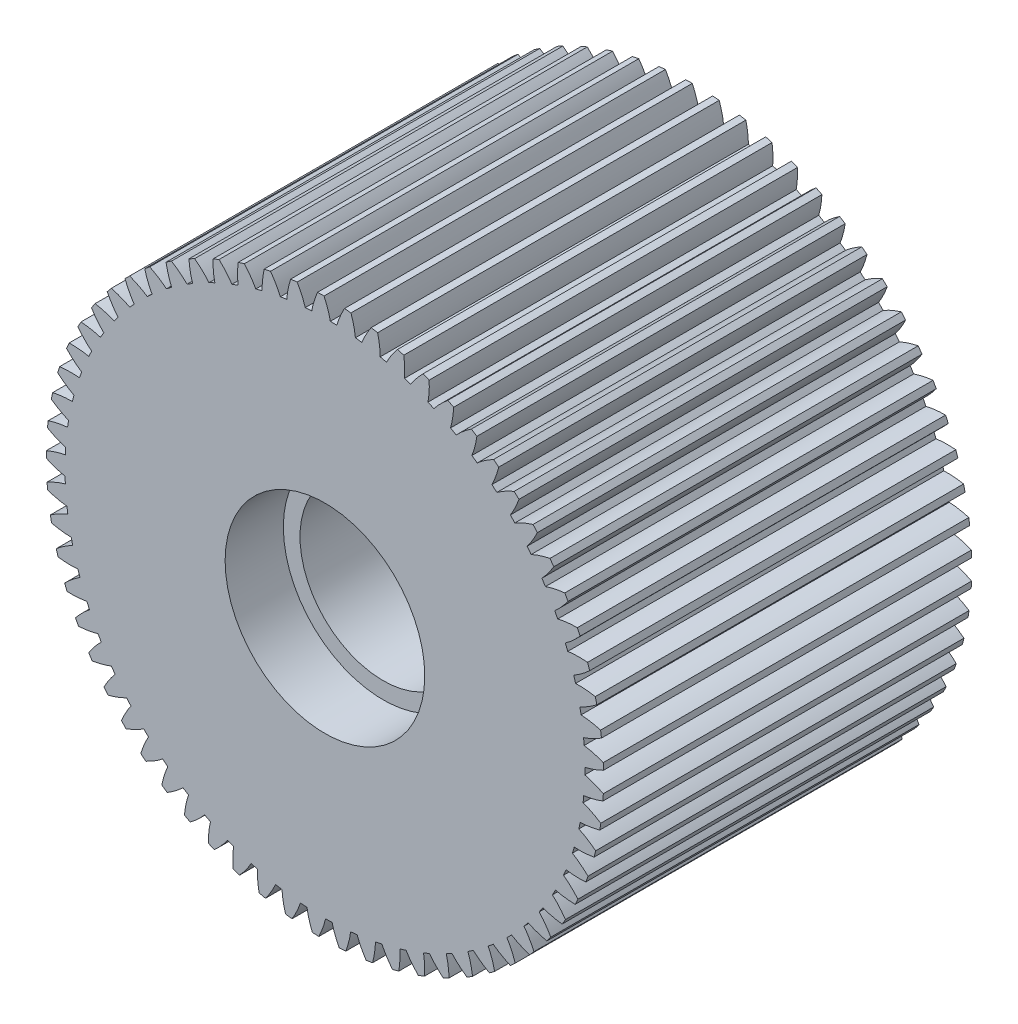
SolidWorks part; units mm, degrees
material "PLA"
ref_plane "Front Plane" through (0, 0, 0) normal (0, 0, 1) x (1, 0, 0)
ref_plane "Top Plane" through (0, 0, 0) normal (0, 1, 0) x (1, 0, 0)
ref_plane "Right Plane" through (0, 0, 0) normal (1, 0, 0) x (0, 0, -1)
sketch "Sketch1" plane through (0, 0, 0) normal (0, 0, 1) x (1, 0, 0)
  circle A0 centre (0, 0) radius 16.75
  dimension "D1" = 33.5
extrude "Boss-Extrude1" add sketch "Sketch1" along normal mid plane 22.1348
sketch "Sketch2" plane through (0, 0, 0) normal (0, 0, 1) x (1, 0, 0)
  line L0 (0, 0) -> (15.27, 0) construction
  line L1 (0, 0) -> (16.2493, -0.1505) construction
  line L2 (0, 0) -> (15.2674, -0.2828) construction
  line L3 (15.27, 0) -> (15.625, 0)
  line L4 (15.2674, -0.2828) -> (15.6223, -0.2894)
  circle A0 centre (0, 0) radius 16.25 construction
  circle A1 centre (0, 0) radius 15.27 construction
  circle A2 centre (0, 0) radius 15.625
  circle A3 centre (0, 0) radius 16.75 construction
  circle A4 centre (0, 0) radius 16.75
  spline S0 degree 4 poles (15.27, 0) (15.2752, 0.0001) (15.2899, 0.0005) (15.3175, 0.0023) (15.3626, 0.0064) (15.4199, 0.0137) (15.4938, 0.0252) (15.5806, 0.0416) (15.6756, 0.0626) (15.7786, 0.0886) (15.8809, 0.1173) (15.9825, 0.1485) (16.0833, 0.1819) (16.2049, 0.2252) (16.35, 0.2808) (16.5183, 0.3514) (16.7076, 0.4379) (16.8987, 0.533) (17.0852, 0.6321) (17.2717, 0.7387) (17.4507, 0.8463) (17.6345, 0.9646) (17.8031, 1.0771) (17.9894, 1.2102) (18.139, 1.3196) (18.3335, 1.4715) (18.4475, 1.5634) (18.5798, 1.6734) (18.638, 1.7237) (18.6739, 1.7546) knots 0 0 0 0 0 0.005377 0.015084 0.028532 0.04661 0.064855 0.092111 0.119476 0.146842 0.174209 0.201575 0.228941 0.256307 0.307035 0.361767 0.4165 0.471232 0.525964 0.580697 0.635429 0.690161 0.744894 0.799626 0.854358 0.909091 0.954545 1 1 1 1 1 construction
  spline S1 degree 4 poles (15.27, 0) (15.2752, 0.0001) (15.2899, 0.0005) (15.3175, 0.0023) (15.3626, 0.0064) (15.4199, 0.0137) (15.4938, 0.0252) (15.5806, 0.0416) (15.6756, 0.0626) (15.7786, 0.0886) (15.8809, 0.1173) (15.9825, 0.1485) (16.0833, 0.1819) (16.2049, 0.2252) (16.35, 0.2808) (16.5183, 0.3514) (16.7076, 0.4379) (16.8987, 0.533) (17.0852, 0.6321) (17.2717, 0.7387) (17.4507, 0.8463) (17.6345, 0.9646) (17.8031, 1.0771) (17.9894, 1.2102) (18.139, 1.3196) (18.2913, 1.4386) (18.3651, 1.4973) (18.4027, 1.5277) knots 0 0 0 0 0 0.005377 0.015084 0.028532 0.04661 0.064855 0.092111 0.119476 0.146842 0.174209 0.201575 0.228941 0.256307 0.307035 0.361767 0.4165 0.471232 0.525964 0.580697 0.635429 0.690161 0.744894 0.799626 0.854358 0.909091 0.909091 0.909091 0.909091 0.909091
  spline S2 degree 4 poles (15.2674, -0.2828) (15.2726, -0.283) (15.2872, -0.2837) (15.3148, -0.286) (15.3598, -0.291) (15.417, -0.2993) (15.4907, -0.3122) (15.5771, -0.3302) (15.6717, -0.3529) (15.7742, -0.3808) (15.876, -0.4114) (15.977, -0.4445) (16.0772, -0.4798) (16.198, -0.5253) (16.342, -0.5836) (16.5089, -0.6573) (16.6966, -0.7473) (16.8859, -0.8459) (17.0705, -0.9485) (17.255, -1.0585) (17.4321, -1.1694) (17.6137, -1.2911) (17.7801, -1.4067) (17.9639, -1.5432) (18.1115, -1.6554) (18.3031, -1.8108) (18.4153, -1.9048) (18.5456, -2.0173) (18.6029, -2.0686) (18.6382, -2.1001) knots 0 0 0 0 0 0.005377 0.015084 0.028532 0.04661 0.064855 0.092111 0.119476 0.146842 0.174209 0.201575 0.228941 0.256307 0.307035 0.361767 0.4165 0.471232 0.525964 0.580697 0.635429 0.690161 0.744894 0.799626 0.854358 0.909091 0.954545 1 1 1 1 1 construction
  spline S3 degree 4 poles (15.2674, -0.2828) (15.2726, -0.283) (15.2872, -0.2837) (15.3148, -0.286) (15.3598, -0.291) (15.417, -0.2993) (15.4907, -0.3122) (15.5771, -0.3302) (15.6717, -0.3529) (15.7742, -0.3808) (15.876, -0.4114) (15.977, -0.4445) (16.0772, -0.4798) (16.198, -0.5253) (16.342, -0.5836) (16.5089, -0.6573) (16.6966, -0.7473) (16.8859, -0.8459) (17.0705, -0.9485) (17.255, -1.0585) (17.4321, -1.1694) (17.6137, -1.2911) (17.7801, -1.4067) (17.9639, -1.5432) (18.1115, -1.6554) (18.2615, -1.7771) (18.3342, -1.8372) (18.3712, -1.8683) knots 0 0 0 0 0 0.005377 0.015084 0.028532 0.04661 0.064855 0.092111 0.119476 0.146842 0.174209 0.201575 0.228941 0.256307 0.307035 0.361767 0.4165 0.471232 0.525964 0.580697 0.635429 0.690161 0.744894 0.799626 0.854358 0.909091 0.909091 0.909091 0.909091 0.909091
  dimension "D1" = 32.5
  dimension "D2" = 30.54
  dimension "D3" = 31.25
  dimension "D4" = 0.531
  dimension "D5" = 0.531
extrude "Cut-Extrude1" cut sketch "Sketch2" against normal through all both and the other way through all contours A2 S3 A4 S1 region at (16.2879, -0.1509, 0)
pattern_circular "CirPattern2" count 65 over 360 about axis through (0, 0, 11.0674) along (0, 0, -1) of "Cut-Extrude1"
sketch "Sketch3" plane through (0, 0, 11.0674) normal (0, 0, 1) x (1, 0, 0)
  circle A0 centre (0, 0) radius 6
  dimension "D1" = 12
extrude "Cut-Extrude2" cut sketch "Sketch3" against normal blind 3.5
sketch "Sketch4" plane through (0, 0, 7.5674) normal (0, 0, 1) x (1, 0, 0)
  circle A0 centre (0, 0) radius 5
  dimension "D1" = 10
extrude "Cut-Extrude3" cut sketch "Sketch4" against normal through all
mirror "Mirror1" about plane through (0, 0, 0) normal (0, 0, 1) of "Cut-Extrude2"
equation "\"Np\"= 65"
equation "\"module\"= 0.5"
equation "\"pressure angle\"= 20.0deg"
equation "\"h_a\"= 0.5"
equation "\"h_b\"= 0.625"
equation "\"clr_tip_root\"= 0.125"
equation "\"dp_p\"= 32.5"
equation "\"db_p\"= 30.540010175542022"
equation "\"D1@Sketch1\"= \"dp_p\" + 2*\"h_a\" "
equation "\"fw_p\"= 22.13479809822934"
equation "\"D1@Boss-Extrude1\"=\"fw_p\""
equation "\"D1@Sketch2\"=\"dp_p\""
equation "\"D2@Sketch2\"= \"db_p\""
equation "\"D3@Sketch2\"=\"dp_p\"- 2*\"h_b\""
equation "\"alpha_p\"= 0.8539582918412485"
equation "\"D4@Sketch2\"= 360 / ( 4 * \"Np\" ) - \"alpha_p\""
equation "\"beta_p\"= 1.0613141855482722"
equation "\"D5@Sketch2\"= 360 / ( 4 * \"Np\" ) - \"alpha_p\""
equation "\"D1@CirPattern2\"=\"Np\""
equation "\"Nr\"= 155"
equation "\"pressure_angle\"= 20.0deg"
equation "\"h_f\"= 0.625"
equation "\"dp_r\"= 77.5"
equation "\"db_r\"= 72.8261781109079"
equation "\"fw_r\"= 22.13479809822934"
equation "\"alpha_r\"= 0.8539582918412449"
equation "\"beta_r\"= 2.869206906263135"
equation "\"bearing_ID\"= 55"
equation "\"bearing_OD\"= 72"
equation "\"bearing_height\"= 9"
equation "\"clearance_planet\"= 1.5"
equation "\"case_dist\"= 6.5"
equation "\"Motor_case_OD_max\"= 112.3"
equation "\"case_mounting_PCD\"= 104.8"
equation "\"bearing mount thickness\"= 8"
equation "\"case_mounting_hole_dia\"= 3"
equation "\"output_mounting_PCD\"= 80"
equation "\"output_mounting_hole_dia\"= 4"
equation "\"clearance_case_mount_holes_shell_thickness\"= 1"
equation "\"motor_case_OD_base\"= 102.8"
equation "\"sec_carrier_thickness\"= 5"
equation "\"sun_coupler_hub_thickness\"= 4"
equation "\"clearance_sun_coupler_sec_carrier\"= 1.5"
equation "\"clearance_motor_and_case\"= 5"
equation "\"motor_OD\"= 87.8"
equation "\"Motor_case_thickness\"= 2.5"
equation "\"Motor_case_ID\"= 97.8"
equation "\"case_mounting_hole_shift\"= 1.0"
equation "\"output_mounting_nut_wrench_size\"= 7"
equation "\"output_mounting_nut_thickness\"= 3.2"
equation "\"case_mounting_hole_allen_socket_dia\"= 5.5"
equation "\"output_mounting_nut_depth\"= 3"
equation "\"case_mounting_bolt_depth\"= 4.5"
equation "\"Ns\"= 25"
equation "\"ring_radial_thickness\"= 5.0"
equation "\"ring_OD\"= 87.5"
equation "\"ring_to_chamfer_clearance\"= 2"
equation "\"Motor_case_OD_base_to_chamfer\"= 5"
equation "\"pattern_offset_from_motor_case_OD_base\"= 3"
equation "\"pattern_bulge_dia\"= 3"
equation "\"pattern_num_bulge\"= 18"
equation "\"pattern_depth\"= 2"
equation "\"motor_height\"= 31.5"
equation "\"case_mounting_wrench_size\"= 5.5"
equation "\"case_mounting_nut_clearance\"= 2"
equation "\"base_plate_thickness\"= 4"
equation "\"case_mounting_nut_thickness\"= 2.4"
equation "\"case_mounting_surface_height\"= 4"
equation "\"motor_mount_hole_PCD\"= 36"
equation "\"motor_mount_hole_dia\"= 4"
equation "\"motor_mount_hole_num\"= 4"
equation "\"central_hole_offset_from_motor_mount_PCD\"= 5"
equation "\"wire_slot_dist_from_center\"= 40"
equation "\"wire_slot_length\"= 10"
equation "\"wire_slot_radius\"= 2.5"
equation "\"driver_upper_holes_dist_from_center\"= 29"
equation "\"driver_lower_holes_dist_from_center\"= 13"
equation "\"driver_side_holes_dist_from_center\"= 22.5"
equation "\"driver_mount_holes_dia\"= 3"
equation "\"driver_mount_inserts_OD\"= 4.8"
equation "\"driver_mount_thickness\"= 1.5"
equation "\"driver_mount_height\"= 6"
equation "\"air_flow_hole_offset\"= 3"
equation "\"num_planet\"= 3"
equation "\"planet_pin_bolt_dia\"= 5"
equation "\"planet_pin_socket_head_dia\"= 8.5"
equation "\"carrier_PCD\"= 45.0"
equation "\"planet_shaft_dia\"= 8"
equation "\"planet_shaft_step_offset\"= 1"
equation "\"carrier_trapezoidal_support_sun_offset\"= 5"
equation "\"carrier_trapezoidal_support_hole_PCD_offset_bearing_ID\"= 4"
equation "\"carrier_trapezoidal_support_hole_dia\"= 3"
equation "\"carrier_trapezoidal_support_hole_socket_head_dia\"= 5.5"
equation "\"carrier_bearing_step_width\"= 1.5"
equation "\"standard_clearance_1_5mm\"= 1.5"
equation "\"standard_fillet_1_5mm\"= 1.5"
equation "\"sun_shaft_bearing_OD\"= 16"
equation "\"sun_shaft_bearing_width\"= 5"
equation "\"standard_bearing_insertion_chamfer\"= 0.5"
equation "\"carrier_trapezoidal_support_hole_wrench_size\"= 5.5"
equation "\"planet_pin_bolt_wrench_size\"= 8"
equation "\"planet_bearing_OD\"= 12"
equation "\"planet_bearing_width\"= 3.5"
equation "\"planet_bore\"= 10"
equation "\"D1@Cut-Extrude2\"=\"planet_bearing_width\""
equation "\"D1@Sketch3\"=\"planet_bearing_OD\""
equation "\"D1@Sketch4\"=\"planet_bore\""
